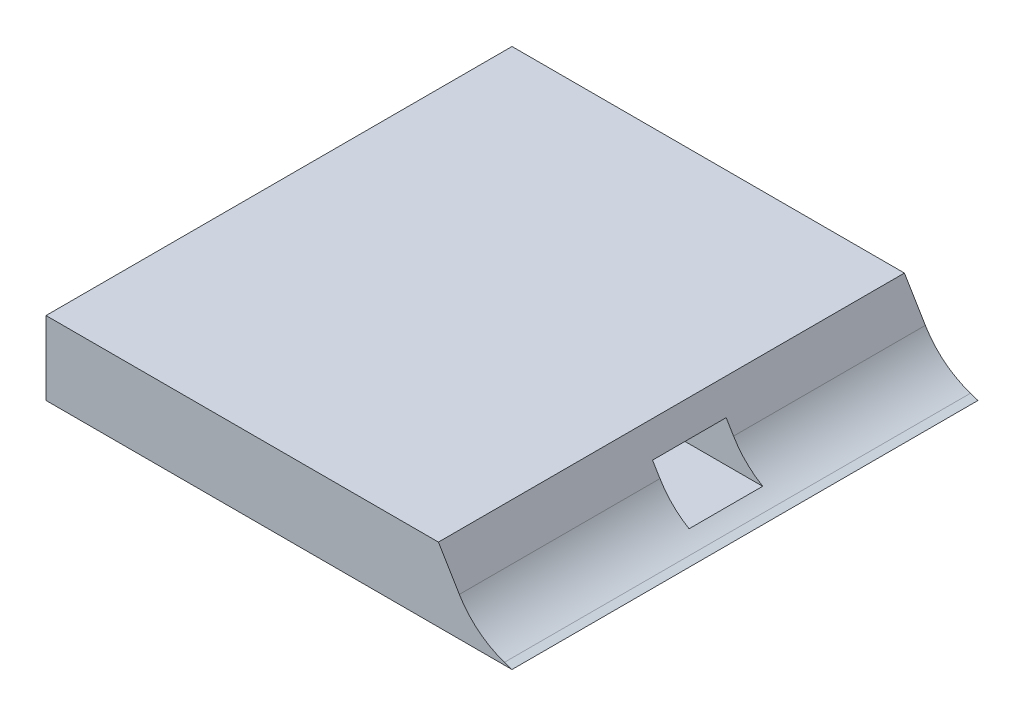
SolidWorks part; units mm, degrees
ref_plane "Front Plane" through (0, 0, 0) normal (0, 0, 1) x (1, 0, 0)
ref_plane "Top Plane" through (0, 0, 0) normal (0, 1, 0) x (1, 0, 0)
ref_plane "Right Plane" through (0, 0, 0) normal (1, 0, 0) x (0, 0, -1)
sketch "Sketch1" plane through (0, 0, 0) normal (0, 1, 0) x (1, 0, 0)
  line L1 (-45, -47.5) -> (45, -47.5)
  line L2 (-45, -47.5) -> (-45, 47.5)
  line L3 (-45, 47.5) -> (45, 47.5)
  line L4 (45, -47.5) -> (45, 47.5)
  line L5 (-45, -47.5) -> (45, 47.5) construction
  line L6 (-45, 47.5) -> (45, -47.5) construction
  point P0 (0, 0)
  dimension "D1" = 95
  dimension "D2" = 90
extrude "Boss-Extrude3" add sketch "Sketch1" along normal blind 15
sketch "Sketch5" plane through (45, 0, 0) normal (1, 0, 0) x (0, 0, -1)
  line L0 (-47.5, 0) -> (47.5, 0) construction
  line L1 (-6.6, 2) -> (8.4, 2)
  line L2 (-6.6, 2) -> (-6.6, 10.4)
  line L3 (-6.6, 10.4) -> (8.4, 10.4)
  line L4 (8.4, 2) -> (8.4, 10.4)
  dimension "D1" = 15
  dimension "D2" = 8.4
  dimension "D3" = 2
extrude "Cut-Extrude3" cut sketch "Sketch5" against normal blind 40
sketch "Sketch7" plane through (45, 0, 0) normal (1, 0, 0) x (0, 0, -1)
  line L1 (-47.5, 0) -> (47.5, 0)
  line L2 (-47.5, 0) -> (-47.5, 15)
  line L3 (-47.5, 15) -> (47.5, 15)
  line L4 (47.5, 0) -> (47.5, 15)
extrude "Boss-Extrude4" add sketch "Sketch7" along normal blind 5
sketch "Sketch8" plane through (0, 0, 47.5) normal (0, 0, 1) x (1, 0, 0)
  line L0 (-45, 15) -> (50, 15) construction
  line L1 (42.5, 2.5) -> (50, 0)
  line L2 (50, 0) -> (50, 15)
  line L3 (50, 15) -> (35, 15)
  line L5 (35, 15) -> (42.5, 2.5)
  dimension "D1" = 15
extrude "Cut-Extrude4" cut sketch "Sketch8" against normal blind 100
fillet "Fillet6" radius 17 1 edges at (42.5, 2.5, 27.05)
